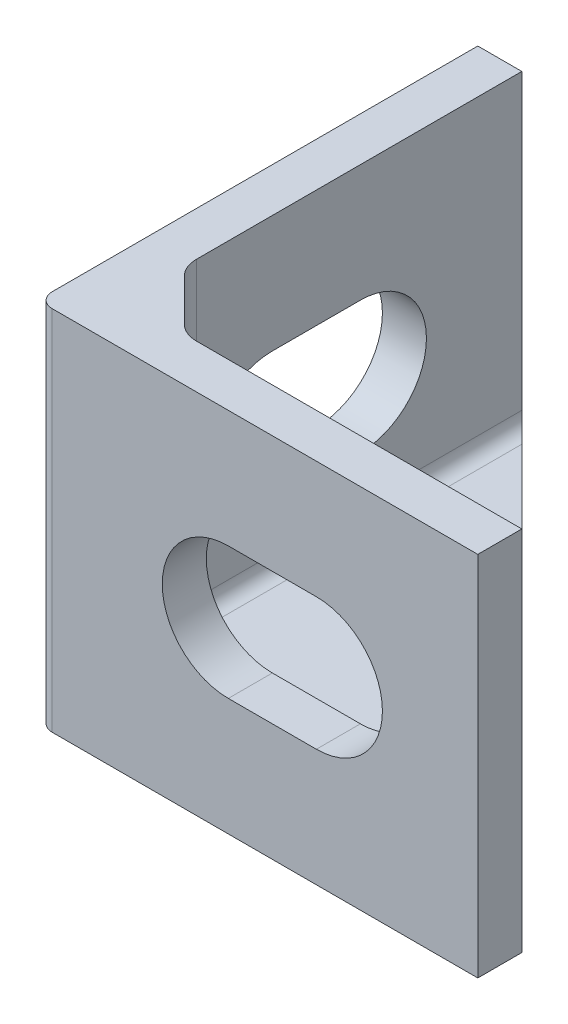
SolidWorks part; units mm, degrees
ref_plane "정면" through (0, 0, 0) normal (0, 0, 1) x (1, 0, 0)
ref_plane "윗면" through (0, 0, 0) normal (0, 1, 0) x (1, 0, 0)
ref_plane "우측면" through (0, 0, 0) normal (1, 0, 0) x (0, 0, -1)
sketch "스케치1" plane through (0, 0, 0) normal (0, 0, 1) x (1, 0, 0)
  line L0 (0, 0) -> (37.1233, 0) construction
  line L1 (0, 0) -> (0, 28.5317) construction
  line L2 (0, 12.5) -> (0, -12.5)
  line L3 (0, 12.5) -> (30, 12.5)
  line L4 (30, 12.5) -> (30, -12.5)
  line L5 (13, 4.5) -> (19, 4.5)
  line L6 (13, -4.5) -> (19, -4.5)
  line L7 (0, -12.5) -> (30, -12.5)
  circle A0 centre (19, 0) radius 4.5
  circle A1 centre (13, 0) radius 4.5
  point P6 (0, 0)
  point P15 (0, 0)
  point P16 (0, 0)
  point P20 (30, 0)
  dimension "D3" = 9
  dimension "D5" = 9
  dimension "D1" = 25
  dimension "D2" = 30
  dimension "D4" = 11
  dimension "D6" = 6
sketch "스케치2" plane through (0, 0, 0) normal (1, 0, 0) x (0, 0, -1)
  line L0 (0, 0) -> (2.0924, 0) construction
  line L1 (0, 0) -> (0, 23.2127) construction
  line L2 (0, 12.5) -> (0, -12.5)
  line L3 (0, 12.5) -> (30, 12.5)
  line L4 (30, 12.5) -> (30, -12.5)
  line L5 (13, 4.5) -> (19, 4.5)
  line L6 (13, -4.5) -> (19, -4.5)
  line L7 (0, -12.5) -> (30, -12.5)
  line L10 (0, 12.5) -> (0, -12.5) construction
  circle A0 centre (19, 0) radius 4.5
  circle A1 centre (13, 0) radius 4.5
  point P5 (0, 0)
  point P16 (30, 0)
  point P19 (0, 0)
  dimension "D3" = 9
  dimension "D5" = 9
  dimension "D1" = 25
  dimension "D2" = 30
  dimension "D4" = 11
  dimension "D6" = 6
extrude "보스-돌출1" add sketch "스케치2" along normal blind 3 contours L2 L7 L4 L3 A1 L5 A0 L6 region at (0, 12.1095, -15)
extrude "보스-돌출2" add sketch "스케치1" against normal blind 3 contours L2 L7 L4 L3 A1 L5 A0 L6 region at (15, 12.1095, 0)
sketch "스케치3" plane through (0, 0, -3) normal (0, 0, -1) x (-1, 0, 0)
  line L0 (-30, -12.5) -> (-3, -12.5)
  line L1 (-3, -12.5) -> (-30, -12.5) construction
  line L2 (-3, 12.5) -> (-3, -12.5) construction
  line L3 (-3, -12.5) -> (-3, -8.5)
  line L4 (-3, -8.5) -> (-30, -8.5)
  line L5 (-30, 12.5) -> (-30, -12.5) construction
  line L6 (-30, -8.5) -> (-30, -12.5)
  dimension "D1" = 4
extrude "보스-돌출3" add sketch "스케치3" along normal blind 27
sketch "스케치5" plane through (0, -8.5, 0) normal (0, 1, 0) x (1, 0, 0)
  line L0 (3, 3) -> (30, 3)
  line L1 (3, 3) -> (30, 3)
  line L2 (3, 30) -> (3, 3)
  line L3 (3, 30) -> (3, 3)
  line L4 (30, 30) -> (30, 3)
  line L5 (30, 3) -> (30, 0)
  line L6 (30, 3) -> (30, 0)
  line L7 (30, 30) -> (30, 3)
  line L8 (3, 30) -> (30, 30)
  line L9 (3, 30) -> (0, 30)
  line L10 (3, 30) -> (0, 30)
  line L11 (3, 30) -> (30, 30)
  line L12 (30, 3) -> (3, 30)
  line L13 (6, 3) -> (3, 6)
  line M2 (30, 3) -> (30, 30)
  line M3 (30, 30) -> (3, 30)
  dimension "D1" = 3
  dimension "D2" = 3
extrude "컷-돌출1" cut sketch "스케치5" against normal blind 27 contours L12 M2 M3 region at (21, -8.5, -21)
fillet "필렛1" radius 1 1 edges at (0, 0, 0)
chamfer "모따기1" distance 4 angle 45 1 edges at (3, 2, -3)
fillet "필렛2" radius 2 2 edges at (7, 2, -3) (3, 2, -7)
fillet "필렛3" radius 1 5 edges at (18.9142, -8.5, -3) (7.0631, -8.5, -3.1522) (5, -8.5, -5) (3.1522, -8.5, -7.0631) (3, -8.5, -18.9142)
